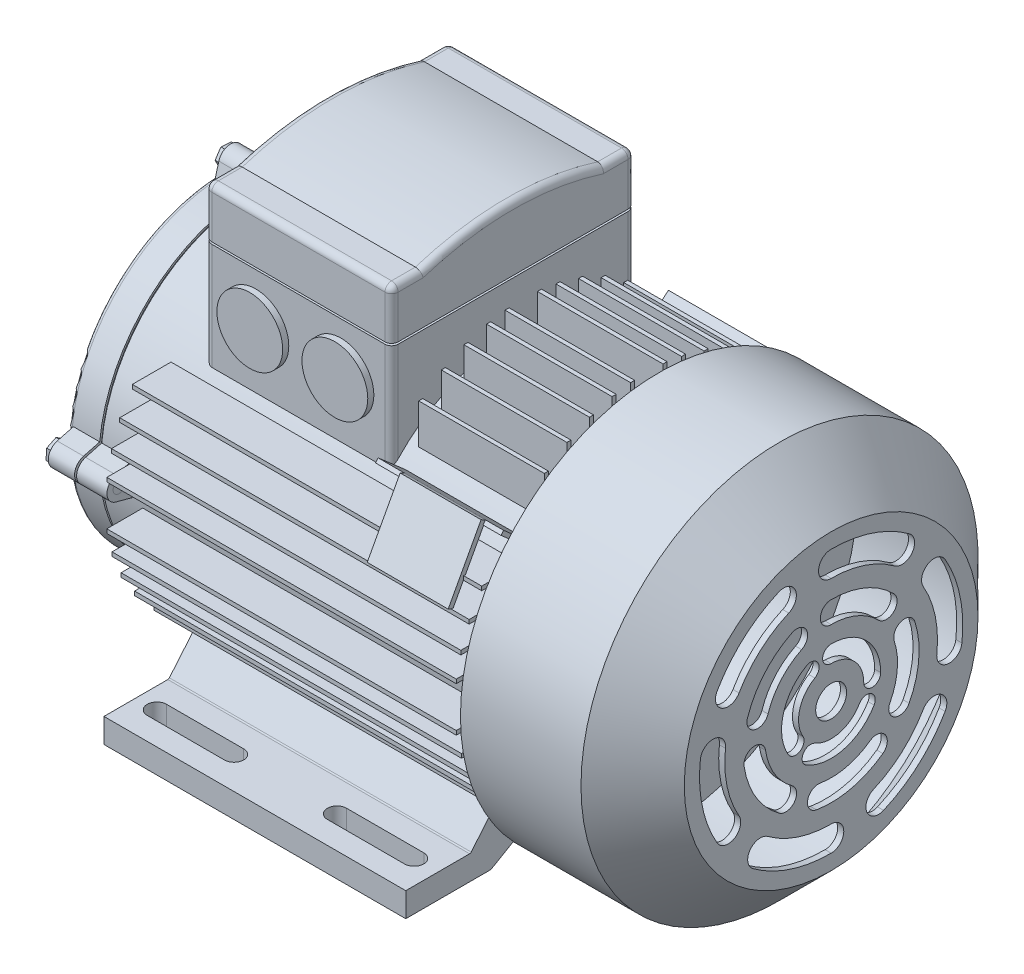
SolidWorks part; units mm, degrees
ref_plane "Front Plane" through (0, 0, 0) normal (0, 0, 1) x (1, 0, 0)
ref_plane "Top Plane" through (0, 0, 0) normal (0, 1, 0) x (1, 0, 0)
ref_plane "Right Plane" through (0, 0, 0) normal (1, 0, 0) x (0, 0, -1)
sketch "Sketch1" plane through (0, 0, 0) normal (0, 0, 1) x (1, 0, 0)
  line L0 (-1000, 0) -> (49000, 0) construction
  line L1 (0, -1000) -> (0, 49000) construction
  line L2 (0, 20) -> (0, 44.9999)
  line L3 (304.9999, 0) -> (304.9999, 72.5)
  line L4 (0, 44.9999) -> (5, 44.9999)
  line L5 (5, 44.9999) -> (5, 60)
  line L6 (5, 60) -> (6, 60)
  line L7 (6, 60) -> (6, 78)
  line L8 (6, 78) -> (219.9998, 78)
  line L9 (304.9999, 72.5) -> (279.4998, 98.0001)
  line L10 (279.4998, 98.0001) -> (219.9998, 98.0001)
  line L11 (219.9998, 98.0001) -> (219.9998, 78)
  line L12 (301.9999, 0) -> (301.9999, 71.2573)
  line L13 (301.9999, 71.2573) -> (278.2572, 95.0001)
  line L14 (278.2572, 95.0001) -> (222.9998, 95.0001)
  line L15 (222.9998, 95.0001) -> (222.9998, 68)
  line L16 (222.9998, 95.0001) -> (222.9998, 78) construction
  line L17 (222.9998, 68) -> (15, 68)
  line L18 (15, 68) -> (15, 20)
  line L19 (15, 20) -> (0, 20)
  line L20 (301.9999, 0) -> (304.9999, 0)
  dimension "D1" = 5
  dimension "D2" = 24.9999
  dimension "D3" = 39.9999
  dimension "D4" = 120
  dimension "D5" = 1
  dimension "D6" = 155.9999
  dimension "D7" = 304.9999
  dimension "D8" = 145
  dimension "D9" = 45
  dimension "D10" = 85.0001
  dimension "D11" = 196.0001
  dimension "D13" = 10
  dimension "D14" = 15
  dimension "D12" = 3
revolve "Revolve1" add sketch "Sketch1" angle 360 about L0
ref_plane "Plane1" through (43.9999, 0, 0) normal (-1, 0, 0) x (0, 0, 1)
sketch "Sketch2" plane through (43.9999, 0, 0) normal (-1, 0, 0) x (0, 0, 1)
  line L0 (-98.0001, -100.0001) -> (98.0001, -100.0001) construction
  line L1 (98.0001, -100.0001) -> (98.0001, -88.0001)
  line L2 (98.0001, -88.0001) -> (66.0001, -88.0001)
  line L3 (66.0001, -88.0001) -> (45.3874, -63.4348)
  line L4 (56.0001, -100.0001) -> (15.2779, -76.4891)
  line L5 (-98.0001, -100.0001) -> (-98.0001, -88.0001)
  line L6 (-98.0001, -88.0001) -> (-66.0001, -88.0001)
  line L7 (-66.0001, -88.0001) -> (-45.3874, -63.4348)
  line L8 (-56.0001, -100.0001) -> (-15.2779, -76.4891)
  line L9 (98.0001, -100.0001) -> (56.0001, -100.0001)
  line L10 (-56.0001, -100.0001) -> (-98.0001, -100.0001)
  circle A0 centre (0, 0) radius 68
  circle A1 centre (0, 0) radius 78
  circle A2 centre (0, 0) radius 78 construction
  circle A3 centre (0, 0) radius 68 construction
  arc A4 (-45.3874, -63.4348) -> (-15.2779, -76.4891) centre (0, 0) ccw
  arc A5 (15.2779, -76.4891) -> (45.3874, -63.4348) centre (0, 0) ccw
  point P8 (0, -100.0001)
  dimension "D1" = 100.0001
  dimension "D2" = 196.0001
  dimension "D3" = 12
  dimension "D4" = 41.9999
  dimension "D5" = 20
  dimension "D6" = 10
  dimension "D7" = 30
  dimension "D8" = 41.9999
  dimension "D9" = 20
  dimension "D10" = 10
extrude "Boss-Extrude1" add sketch "Sketch2" against normal blind 149 contours A4 L7 L6 L5 L10 L8 | L1 L2 L3 A5 L4 L9 region at (43.9999, -85.9903, -56.5508)
ref_plane "Plane2" through (102.0001, 0, 0) normal (-1, 0, 0) x (0, 0, 1)
sketch "Sketch3" plane through (102.0001, 0, 0) normal (-1, 0, 0) x (0, 0, 1)
  line L0 (98.0001, -88.0001) -> (98.0001, -100.0001)
  line L1 (66.0001, -88.0001) -> (98.0001, -88.0001)
  line L2 (45.3874, -63.4348) -> (66.0001, -88.0001)
  line L3 (15.2779, -76.4891) -> (56.0001, -100.0001)
  line L4 (56.0001, -100.0001) -> (98.0001, -100.0001)
  line L5 (-45.3874, -63.4348) -> (-66.0001, -88.0001)
  line L6 (-66.0001, -88.0001) -> (-98.0001, -88.0001)
  line L7 (-98.0001, -88.0001) -> (-98.0001, -100.0001)
  line L8 (-98.0001, -100.0001) -> (-56.0001, -100.0001)
  line L9 (-15.2779, -76.4891) -> (-56.0001, -100.0001)
  line L10 (-15.2779, -76.4891) -> (-56.0001, -100.0001) construction
  line L11 (-98.0001, -100.0001) -> (-56.0001, -100.0001) construction
  line L12 (-98.0001, -88.0001) -> (-98.0001, -100.0001) construction
  line L13 (-66.0001, -88.0001) -> (-98.0001, -88.0001) construction
  line L14 (-45.3874, -63.4348) -> (-66.0001, -88.0001) construction
  line L15 (56.0001, -100.0001) -> (98.0001, -100.0001) construction
  line L16 (15.2779, -76.4891) -> (56.0001, -100.0001) construction
  line L17 (45.3874, -63.4348) -> (66.0001, -88.0001) construction
  line L18 (66.0001, -88.0001) -> (98.0001, -88.0001) construction
  line L19 (98.0001, -88.0001) -> (98.0001, -100.0001) construction
  line L20 (0, -1000) -> (0, 49000) construction
  line L21 (-60, 128) -> (60, 128) construction
  line L22 (-60, 128) -> (-60, 49.8397)
  line L23 (60, 128) -> (60, 49.8397)
  line L24 (45, 128) -> (60, 128)
  line L25 (-45, 128) -> (-60, 128)
  circle A0 centre (0, 0) radius 68
  arc A1 (-15.2779, -76.4891) -> (15.2779, -76.4891) centre (0, 0) ccw
  arc A2 (45.3874, -63.4348) -> (-45.3874, -63.4348) centre (0, 0) ccw
  arc A3 (45.3874, -63.4348) -> (-45.3874, -63.4348) centre (0, 0) ccw construction
  arc A4 (-15.2779, -76.4891) -> (15.2779, -76.4891) centre (0, 0) ccw construction
  circle A5 centre (0, 0) radius 68 construction
  arc A6 (-60, 49.8397) -> (60, 49.8397) centre (0, 0) cw
  arc A7 (-45, 128) -> (45, 128) centre (0, -13.1434) cw
  point P21 (0, 128)
  point P28 (0, 135)
  dimension "D1" = 120
  dimension "D2" = 128
  dimension "D3" = 7
  dimension "D4" = 15
  dimension "D5" = 15
extrude "Boss-Extrude2" add sketch "Sketch3" along normal mid plane 92.0001 contours L22 A6 L23 L24 A7 L25
sketch "Sketch4" plane through (0, 0, 60) normal (0, 0, 1) x (1, 0, 0)
  line L0 (81.0001, 78.0001) -> (123, 78.0001) construction
  line L1 (102.0001, 49.8397) -> (102.0001, 128) construction
  line L4 (148.0001, 49.8397) -> (148.0001, 128)
  line L5 (148.0001, 128) -> (56, 128)
  line L6 (56, 128) -> (56, 49.8397)
  line L7 (56, 49.8397) -> (148.0001, 49.8397)
  line L8 (148.0001, 49.8397) -> (148.0001, 128)
  line L9 (148.0001, 128) -> (56, 128)
  line L10 (56, 128) -> (56, 49.8397)
  line L11 (56, 49.8397) -> (148.0001, 49.8397)
  circle A0 centre (81.0001, 78.0001) radius 16.25
  circle A1 centre (123, 78.0001) radius 16.25
  point P10 (102.0001, 78.0001)
  dimension "D3" = 32.5001
  dimension "D4" = 78.0001
  dimension "D2" = 41.9999
  dimension "D1" = 0
extrude "Boss-Extrude3" add sketch "Sketch4" along normal blind 3 contours A0 | A1 region at (81.0001, 78.0001, 60) region at (123, 78.0001, 60)
sketch "Sketch5" plane through (0, 0, 60) normal (0, 0, 1) x (1, 0, 0)
  line L0 (56, 128) -> (56, 49.8397) construction
  line L1 (56, 128) -> (148.0001, 128) construction
  point P0 (56, 103)
  dimension "D1" = 24.9999
ref_plane "Plane3" through (0, 103, 0) normal (0, 1, 0) x (1, 0, 0)
sketch "Sketch6" plane through (0, 103, 0) normal (0, 1, 0) x (1, 0, 0)
  line L0 (148.0001, 60) -> (148.0001, -60)
  line L1 (56, 60) -> (56, -60)
  line L2 (148.0001, -60) -> (56, -60)
  line L3 (148.0001, 60) -> (56, 60)
  line L4 (148.0001, 60) -> (56, 60)
  line L5 (148.0001, -60) -> (56, -60)
  line L6 (56, 60) -> (56, -60)
  line L7 (148.0001, 60) -> (148.0001, -60)
  line L8 (57, 59) -> (57, -59)
  line L9 (147.0001, -59) -> (57, -59)
  line L10 (147.0001, 59) -> (147.0001, -59)
  line L11 (147.0001, 59) -> (57, 59)
  dimension "D1" = 1
extrude "Cut-Extrude1" cut sketch "Sketch6" against normal mid plane 1 contours L11 L8 L9 L10 | L4 L6 L5 L7
ref_plane "Plane4" through (22, 0, 0) normal (-1, 0, 0) x (0, 0, 1)
sketch "Sketch7" plane through (22, 0, 0) normal (-1, 0, 0) x (0, 0, 1)
  circle A0 centre (0, 0) radius 68
  circle A1 centre (0, 0) radius 78
  circle A2 centre (0, 0) radius 78
  circle A3 centre (0, 0) radius 68 construction
  circle A4 centre (0, 0) radius 77
  dimension "D1" = 1
extrude "Cut-Extrude2" cut sketch "Sketch7" against normal mid plane 1 contours A4 | A2
sketch "Sketch8" plane through (22.5, 0, 0) normal (-1, 0, 0) x (0, 0, 1)
  line L0 (0, -1000) -> (0, 49000) construction
  line L1 (-5.7955, 85.5529) -> (-7.9276, 77.5961)
  line L2 (5.7955, 85.5529) -> (7.9276, 77.5961)
  circle A0 centre (0, 0) radius 78
  circle A1 centre (0, 0) radius 77
  circle A2 centre (0, 0) radius 68
  circle A3 centre (0, 0) radius 68 construction
  circle A4 centre (0, 0) radius 77 construction
  circle A5 centre (0, 0) radius 78 construction
  arc A6 (-5.7955, 85.5529) -> (5.7955, 85.5529) centre (0, 84) cw
  arc A7 (-7.9276, 77.5961) -> (7.9276, 77.5961) centre (0, 0) cw
  point P16 (0, 78)
  dimension "D2" = 6
  dimension "D1" = 30
  dimension "D3" = 6
extrude "Boss-Extrude4" add sketch "Sketch8" against normal blind 15
sketch "Sketch9" plane through (21.5, 0, 0) normal (1, 0, 0) x (0, 0, -1)
  line L2 (-5.7955, 85.5529) -> (-7.9276, 77.5961)
  line L3 (7.9276, 77.5961) -> (5.7955, 85.5529)
  line L4 (-5.7955, 85.5529) -> (-7.9276, 77.5961)
  line L5 (7.9276, 77.5961) -> (5.7955, 85.5529)
  circle A0 centre (0, 0) radius 77
  circle A1 centre (0, 0) radius 68
  circle A2 centre (0, 0) radius 78
  circle A3 centre (0, 0) radius 78
  circle A4 centre (0, 0) radius 68
  circle A5 centre (0, 0) radius 77
  arc A8 (-7.9276, 77.5961) -> (7.9276, 77.5961) centre (0, 0) ccw
  arc A9 (5.7955, 85.5529) -> (-5.7955, 85.5529) centre (0, 84) ccw
  arc A10 (-7.9276, 77.5961) -> (7.9276, 77.5961) centre (0, 0) ccw
  arc A11 (5.7955, 85.5529) -> (-5.7955, 85.5529) centre (0, 84) ccw
  circle M6 centre (0, 0) radius 78
  dimension "D1" = 0
extrude "Boss-Extrude5" add sketch "Sketch9" against normal blind 13 contours L5 A11 L4 M6 region at (21.5, 83.0848, 0)
sketch "Sketch10" plane through (8.5, 0, 0) normal (-1, 0, 0) x (0, 0, 1)
  circle A0 centre (0, 84) radius 3
  dimension "D1" = 6
extrude "Cut-Extrude3" cut sketch "Sketch10" against normal up to surface (28.9999 mm away) up to face at (37.4999, 82.7872, 0)
pattern_circular "CirPattern1" count 4 over 360 about axis through (-1000, 0, 0) along (-1, 0, 0) of "Cut-Extrude3", "Boss-Extrude5", "Boss-Extrude4"
fillet "Fillet1" radius 2 1 edges at (6, 0, 78)
ref_plane "Plane5" through (214.9998, 0, 0) normal (-1, 0, 0) x (0, 0, 1)
sketch "Sketch11" plane through (214.9998, 0, 0) normal (-1, 0, 0) x (0, 0, 1)
  line L0 (-1000, 0) -> (49000, 0) construction
  line L1 (95.0713, -10) -> (77.3563, -10)
  line L2 (95.0713, -10) -> (95.0713, -12)
  line L3 (95.0713, -12) -> (77.0714, -12)
  line L4 (95.0713, 10) -> (77.3563, 10)
  line L5 (95.0713, 10) -> (95.0713, 12)
  line L6 (95.0713, 12) -> (77.0714, 12)
  line L7 (92.4853, -21.1501) -> (75.0778, -21.1501)
  line L8 (92.4853, -21.1501) -> (92.4853, -23.1501)
  line L9 (92.4853, -23.1501) -> (74.4854, -23.1501)
  line L10 (88.0535, -32.3002) -> (70.9979, -32.3002)
  line L11 (88.0535, -32.3002) -> (88.0535, -34.3002)
  line L12 (88.0535, -34.3002) -> (70.0535, -34.3002)
  line L13 (81.3898, -43.4503) -> (64.7771, -43.4503)
  line L14 (81.3898, -43.4503) -> (81.3898, -45.4503)
  line L15 (81.3898, -45.4503) -> (63.3898, -45.4503)
  line L16 (71.6693, -56.6003) -> (53.6693, -56.6003)
  line L17 (71.6693, -56.6003) -> (71.6693, -54.6003)
  line L18 (71.6693, -54.6003) -> (55.7028, -54.6003)
  line L19 (88.7128, 32.3002) -> (70.9979, 32.3002)
  line L20 (88.7128, 32.3002) -> (88.7128, 34.3002)
  line L21 (88.7128, 34.3002) -> (70.0535, 34.3002)
  line L22 (92.7927, 23.1501) -> (74.4854, 23.1501)
  line L23 (92.7927, 23.1501) -> (92.7927, 21.1501)
  line L24 (92.7927, 21.1501) -> (75.0778, 21.1501)
  line L25 (82.4921, 43.4503) -> (64.7771, 43.4503)
  line L26 (82.4921, 43.4503) -> (82.4921, 45.4503)
  line L27 (82.4921, 45.4503) -> (63.3898, 45.4503)
  circle A0 centre (0, 0) radius 78
  circle A1 centre (0, 0) radius 68
  circle A2 centre (0, 0) radius 68 construction
  circle A3 centre (0, 0) radius 78
  arc A4 (55.7028, -54.6003) -> (53.6693, -56.6003) centre (0, 0) cw
  dimension "D1" = 10
  dimension "D2" = 10
  dimension "D3" = 2
  dimension "D4" = 17.715
  dimension "D5" = 18
  dimension "D6" = 11.1501
  dimension "D7" = 11.1501
  dimension "D8" = 11.1501
  dimension "D9" = 11.1501
  dimension "D10" = 11.1501
  dimension "D11" = 11.1501
  dimension "D12" = 11.1501
ref_plane "Plane6" through (42.4999, 0, 0) normal (1, 0, 0) x (0, 0, -1)
extrude "Boss-Extrude6" add sketch "Sketch11" along normal up to surface (172.4999 mm away) contours A3 L25 L26 L27 | A3 L19 L20 L21 | A3 L24 L23 L22 | A3 L4 L5 L6 | A3 L3 L2 L1 | A3 L9 L8 L7 | A3 L12 L11 L10 | A3 L15 L14 L13 | A3 L16 L17 L18 region at (214.9998, -11.0026, 86.1446) region at (214.9998, -22.1556, 83.635) region at (214.9998, 11.0026, 86.1446) region at (214.9998, -33.3091, 79.2903) region at (214.9998, 22.1556, 83.7888) region at (214.9998, -44.4636, 72.7358) region at (214.9998, 33.3088, 79.6201) region at (214.9998, -55.6203, 63.1737) region at (214.9998, 44.4628, 73.2873) up to plane "Plane6"
sketch "Sketch12" plane through (214.9998, 0, 0) normal (1, 0, 0) x (0, 0, -1)
  line L0 (-71.6693, -56.6003) -> (-53.6693, -56.6003)
  line L1 (-71.6693, -56.6003) -> (-71.6693, -54.6003)
  line L2 (-71.6693, -54.6003) -> (-55.7028, -54.6003)
  line L3 (-81.3898, -45.4503) -> (-63.3898, -45.4503)
  line L4 (-81.3898, -43.4503) -> (-81.3898, -45.4503)
  line L5 (-81.3898, -43.4503) -> (-64.7771, -43.4503)
  line L6 (-88.0535, -34.3002) -> (-70.0535, -34.3002)
  line L7 (-88.0535, -32.3002) -> (-88.0535, -34.3002)
  line L8 (-88.0535, -32.3002) -> (-70.9979, -32.3002)
  line L9 (-92.4853, -23.1501) -> (-74.4854, -23.1501)
  line L10 (-92.4853, -21.1501) -> (-92.4853, -23.1501)
  line L11 (-92.4853, -21.1501) -> (-75.0778, -21.1501)
  line L12 (-95.0713, -12) -> (-77.0714, -12)
  line L13 (-95.0713, -10) -> (-95.0713, -12)
  line L14 (-95.0713, -10) -> (-77.3563, -10)
  line L15 (-95.0713, 10) -> (-77.3563, 10)
  line L16 (-95.0713, 10) -> (-95.0713, 12)
  line L17 (-95.0713, 12) -> (-77.0714, 12)
  line L18 (-92.7927, 21.1501) -> (-75.0778, 21.1501)
  line L19 (-92.7927, 23.1501) -> (-92.7927, 21.1501)
  line L20 (-92.7927, 23.1501) -> (-74.4854, 23.1501)
  line L21 (-88.7128, 32.3002) -> (-70.9979, 32.3002)
  line L22 (-88.7128, 32.3002) -> (-88.7128, 34.3002)
  line L23 (-88.7128, 34.3002) -> (-70.0535, 34.3002)
  line L24 (-82.4921, 43.4503) -> (-64.7771, 43.4503)
  line L25 (-82.4921, 43.4503) -> (-82.4921, 45.4503)
  line L26 (-82.4921, 45.4503) -> (-63.3898, 45.4503)
  line L27 (-82.4921, 45.4503) -> (-63.3898, 45.4503)
  line L28 (-82.4921, 43.4503) -> (-82.4921, 45.4503)
  line L29 (-82.4921, 43.4503) -> (-64.7771, 43.4503)
  line L30 (-88.7128, 34.3002) -> (-70.0535, 34.3002)
  line L31 (-88.7128, 32.3002) -> (-88.7128, 34.3002)
  line L32 (-88.7128, 32.3002) -> (-70.9979, 32.3002)
  line L33 (-92.7927, 23.1501) -> (-74.4854, 23.1501)
  line L34 (-92.7927, 23.1501) -> (-92.7927, 21.1501)
  line L35 (-92.7927, 21.1501) -> (-75.0778, 21.1501)
  line L36 (-95.0713, 12) -> (-77.0714, 12)
  line L37 (-95.0713, 10) -> (-95.0713, 12)
  line L38 (-95.0713, 10) -> (-77.3563, 10)
  line L39 (-95.0713, -10) -> (-77.3563, -10)
  line L40 (-95.0713, -10) -> (-95.0713, -12)
  line L41 (-95.0713, -12) -> (-77.0714, -12)
  line L42 (-92.4853, -21.1501) -> (-75.0778, -21.1501)
  line L43 (-92.4853, -21.1501) -> (-92.4853, -23.1501)
  line L44 (-92.4853, -23.1501) -> (-74.4854, -23.1501)
  line L45 (-88.0535, -32.3002) -> (-70.9979, -32.3002)
  line L46 (-88.0535, -32.3002) -> (-88.0535, -34.3002)
  line L47 (-88.0535, -34.3002) -> (-70.0535, -34.3002)
  line L48 (-81.3898, -43.4503) -> (-64.7771, -43.4503)
  line L49 (-81.3898, -43.4503) -> (-81.3898, -45.4503)
  line L50 (-81.3898, -45.4503) -> (-63.3898, -45.4503)
  line L51 (-71.6693, -54.6003) -> (-55.7028, -54.6003)
  line L52 (-71.6693, -56.6003) -> (-71.6693, -54.6003)
  line L53 (-71.6693, -56.6003) -> (-53.6693, -56.6003)
  line L54 (0, -1000) -> (0, 49000) construction
  line L55 (-7, 95.6852) -> (-7, 77.6852)
  line L56 (-7, 95.6852) -> (-9, 95.6852)
  line L57 (-9, 95.6852) -> (-9, 77.479)
  line L58 (-18.1501, 94.3097) -> (-18.1501, 75.8589)
  line L59 (-18.1501, 94.3097) -> (-16.1501, 94.3097)
  line L60 (-16.1501, 94.3097) -> (-16.1501, 76.3097)
  line L61 (-27.3002, 91.0663) -> (-27.3002, 73.0664)
  line L62 (-27.3002, 91.0663) -> (-29.3002, 91.0663)
  line L63 (-29.3002, 91.0663) -> (-29.3002, 72.2876)
  line L64 (-38.4503, 85.8643) -> (-38.4503, 67.8644)
  line L65 (-38.4503, 85.8643) -> (-40.4503, 85.8643)
  line L66 (-40.4503, 85.8643) -> (-40.4503, 66.6916)
  line L67 (-49.6004, 78.198) -> (-49.6004, 60.198)
  line L68 (-49.6004, 78.198) -> (-51.6004, 78.198)
  line L69 (-51.6004, 78.198) -> (-51.6004, 58.4927)
  circle A0 centre (0, 0) radius 68
  arc A1 (-63.3898, 45.4503) -> (-64.7771, 43.4503) centre (0, 0) ccw
  arc A2 (-64.7771, 43.4503) -> (-70.0535, 34.3002) centre (0, 0) ccw
  arc A3 (-70.0535, 34.3002) -> (-70.9979, 32.3002) centre (0, 0) ccw
  arc A4 (-70.9979, 32.3002) -> (-74.4854, 23.1501) centre (0, 0) ccw
  arc A5 (-74.4854, 23.1501) -> (-75.0778, 21.1501) centre (0, 0) ccw
  arc A6 (-75.0778, 21.1501) -> (-77.0714, 12) centre (0, 0) ccw
  arc A7 (-77.0714, 12) -> (-77.3563, 10) centre (0, 0) ccw
  arc A8 (-77.3563, 10) -> (-77.3563, -10) centre (0, 0) ccw
  arc A9 (-77.3563, -10) -> (-77.0714, -12) centre (0, 0) ccw
  arc A10 (-77.0714, -12) -> (-75.0778, -21.1501) centre (0, 0) ccw
  arc A11 (-75.0778, -21.1501) -> (-74.4854, -23.1501) centre (0, 0) ccw
  arc A12 (-74.4854, -23.1501) -> (-70.9979, -32.3002) centre (0, 0) ccw
  arc A13 (-70.9979, -32.3002) -> (-70.0535, -34.3002) centre (0, 0) ccw
  arc A14 (-70.0535, -34.3002) -> (-64.7771, -43.4503) centre (0, 0) ccw
  arc A15 (-64.7771, -43.4503) -> (-63.3898, -45.4503) centre (0, 0) ccw
  arc A16 (-63.3898, -45.4503) -> (-55.7028, -54.6003) centre (0, 0) ccw
  arc A17 (-55.7028, -54.6003) -> (-53.6693, -56.6003) centre (0, 0) ccw
  arc A18 (-53.6693, -56.6003) -> (-63.3898, 45.4503) centre (0, 0) ccw
  arc A19 (-53.6693, -56.6003) -> (-63.3898, 45.4503) centre (0, 0) ccw
  arc A20 (-55.7028, -54.6003) -> (-53.6693, -56.6003) centre (0, 0) ccw
  arc A21 (-63.3898, -45.4503) -> (-55.7028, -54.6003) centre (0, 0) ccw
  arc A22 (-64.7771, -43.4503) -> (-63.3898, -45.4503) centre (0, 0) ccw
  arc A23 (-70.0535, -34.3002) -> (-64.7771, -43.4503) centre (0, 0) ccw
  arc A24 (-70.9979, -32.3002) -> (-70.0535, -34.3002) centre (0, 0) ccw
  arc A25 (-74.4854, -23.1501) -> (-70.9979, -32.3002) centre (0, 0) ccw
  arc A26 (-75.0778, -21.1501) -> (-74.4854, -23.1501) centre (0, 0) ccw
  arc A27 (-77.0714, -12) -> (-75.0778, -21.1501) centre (0, 0) ccw
  arc A28 (-77.3563, -10) -> (-77.0714, -12) centre (0, 0) ccw
  arc A29 (-77.3563, 10) -> (-77.3563, -10) centre (0, 0) ccw
  arc A30 (-77.0714, 12) -> (-77.3563, 10) centre (0, 0) ccw
  arc A31 (-75.0778, 21.1501) -> (-77.0714, 12) centre (0, 0) ccw
  arc A32 (-74.4854, 23.1501) -> (-75.0778, 21.1501) centre (0, 0) ccw
  arc A33 (-70.9979, 32.3002) -> (-74.4854, 23.1501) centre (0, 0) ccw
  arc A34 (-70.0535, 34.3002) -> (-70.9979, 32.3002) centre (0, 0) ccw
  arc A35 (-64.7771, 43.4503) -> (-70.0535, 34.3002) centre (0, 0) ccw
  arc A36 (-63.3898, 45.4503) -> (-64.7771, 43.4503) centre (0, 0) ccw
  circle A37 centre (0, 0) radius 68 construction
  dimension "D3" = 2
  dimension "D6" = 11.1501
  dimension "D7" = 11.1501
  dimension "D1" = 18
  dimension "D2" = 7
  dimension "D4" = 11.1501
  dimension "D5" = 11.1501
ref_plane "Plane7" through (153.0001, 0, 0) normal (1, 0, 0) x (0, 0, -1)
extrude "Boss-Extrude7" add sketch "Sketch12" against normal up to surface (61.9997 mm away) contours A19 L67 L68 L69 | A19 L64 L65 L66 | A19 L61 L62 L63 | A19 L60 L59 L58 | A19 L55 L56 L57 region at (214.9998, 86.6357, 8.0019) region at (214.9998, 85.1988, 17.1542) region at (214.9998, 81.8729, 28.3072) region at (214.9998, 76.5714, 39.4608) region at (214.9998, 68.7701, 50.6154) up to plane "Plane7"
sketch "Sketch13" plane through (214.9998, 0, 0) normal (1, 0, 0) x (0, 0, -1)
  line L0 (-9, 95.6852) -> (-9, 77.479)
  line L1 (-7, 95.6852) -> (-9, 95.6852)
  line L2 (-7, 95.6852) -> (-7, 77.6852)
  line L3 (-18.1501, 94.3097) -> (-18.1501, 75.8589)
  line L4 (-18.1501, 94.3097) -> (-16.1501, 94.3097)
  line L5 (-16.1501, 94.3097) -> (-16.1501, 76.3097)
  line L6 (-29.3002, 91.0663) -> (-29.3002, 72.2876)
  line L7 (-27.3002, 91.0663) -> (-29.3002, 91.0663)
  line L8 (-27.3002, 91.0663) -> (-27.3002, 73.0664)
  line L9 (-40.4503, 85.8643) -> (-40.4503, 66.6916)
  line L10 (-38.4503, 85.8643) -> (-40.4503, 85.8643)
  line L11 (-38.4503, 85.8643) -> (-38.4503, 67.8644)
  line L12 (-51.6004, 78.198) -> (-51.6004, 58.4927)
  line L13 (-49.6004, 78.198) -> (-51.6004, 78.198)
  line L14 (-49.6004, 78.198) -> (-49.6004, 60.198)
  line L15 (-71.6693, -56.6003) -> (-53.6693, -56.6003)
  line L16 (-71.6693, -56.6003) -> (-71.6693, -54.6003)
  line L17 (-71.6693, -54.6003) -> (-55.7028, -54.6003)
  line L18 (-81.3898, -45.4503) -> (-63.3898, -45.4503)
  line L19 (-81.3898, -43.4503) -> (-81.3898, -45.4503)
  line L20 (-81.3898, -43.4503) -> (-64.7771, -43.4503)
  line L21 (-88.0535, -34.3002) -> (-70.0535, -34.3002)
  line L22 (-88.0535, -32.3002) -> (-88.0535, -34.3002)
  line L23 (-88.0535, -32.3002) -> (-70.9979, -32.3002)
  line L24 (-92.4853, -23.1501) -> (-74.4854, -23.1501)
  line L25 (-92.4853, -21.1501) -> (-92.4853, -23.1501)
  line L26 (-92.4853, -21.1501) -> (-75.0778, -21.1501)
  line L27 (-95.0713, -12) -> (-77.0714, -12)
  line L28 (-95.0713, -10) -> (-95.0713, -12)
  line L29 (-95.0713, -10) -> (-77.3563, -10)
  line L30 (-95.0713, 10) -> (-77.3563, 10)
  line L31 (-95.0713, 10) -> (-95.0713, 12)
  line L32 (-95.0713, 12) -> (-77.0714, 12)
  line L33 (-92.7927, 21.1501) -> (-75.0778, 21.1501)
  line L34 (-92.7927, 23.1501) -> (-92.7927, 21.1501)
  line L35 (-92.7927, 23.1501) -> (-74.4854, 23.1501)
  line L36 (-88.7128, 32.3002) -> (-70.9979, 32.3002)
  line L37 (-88.7128, 32.3002) -> (-88.7128, 34.3002)
  line L38 (-88.7128, 34.3002) -> (-70.0535, 34.3002)
  line L39 (-82.4921, 43.4503) -> (-64.7771, 43.4503)
  line L40 (-82.4921, 43.4503) -> (-82.4921, 45.4503)
  line L41 (-82.4921, 45.4503) -> (-63.3898, 45.4503)
  line L42 (-82.4921, 45.4503) -> (-63.3898, 45.4503)
  line L43 (-82.4921, 43.4503) -> (-82.4921, 45.4503)
  line L44 (-82.4921, 43.4503) -> (-64.7771, 43.4503)
  line L45 (-88.7128, 34.3002) -> (-70.0535, 34.3002)
  line L46 (-88.7128, 32.3002) -> (-88.7128, 34.3002)
  line L47 (-88.7128, 32.3002) -> (-70.9979, 32.3002)
  line L48 (-92.7927, 23.1501) -> (-74.4854, 23.1501)
  line L49 (-92.7927, 23.1501) -> (-92.7927, 21.1501)
  line L50 (-92.7927, 21.1501) -> (-75.0778, 21.1501)
  line L51 (-95.0713, 12) -> (-77.0714, 12)
  line L52 (-95.0713, 10) -> (-95.0713, 12)
  line L53 (-95.0713, 10) -> (-77.3563, 10)
  line L54 (-95.0713, -10) -> (-77.3563, -10)
  line L55 (-95.0713, -10) -> (-95.0713, -12)
  line L56 (-95.0713, -12) -> (-77.0714, -12)
  line L57 (-92.4853, -21.1501) -> (-75.0778, -21.1501)
  line L58 (-92.4853, -21.1501) -> (-92.4853, -23.1501)
  line L59 (-92.4853, -23.1501) -> (-74.4854, -23.1501)
  line L60 (-88.0535, -32.3002) -> (-70.9979, -32.3002)
  line L61 (-88.0535, -32.3002) -> (-88.0535, -34.3002)
  line L62 (-88.0535, -34.3002) -> (-70.0535, -34.3002)
  line L63 (-81.3898, -43.4503) -> (-64.7771, -43.4503)
  line L64 (-81.3898, -43.4503) -> (-81.3898, -45.4503)
  line L65 (-81.3898, -45.4503) -> (-63.3898, -45.4503)
  line L66 (-71.6693, -54.6003) -> (-55.7028, -54.6003)
  line L67 (-71.6693, -56.6003) -> (-71.6693, -54.6003)
  line L68 (-71.6693, -56.6003) -> (-53.6693, -56.6003)
  line L69 (-49.6004, 78.198) -> (-49.6004, 60.198)
  line L70 (-49.6004, 78.198) -> (-51.6004, 78.198)
  line L71 (-51.6004, 78.198) -> (-51.6004, 58.4927)
  line L72 (-38.4503, 85.8643) -> (-38.4503, 67.8644)
  line L73 (-38.4503, 85.8643) -> (-40.4503, 85.8643)
  line L74 (-40.4503, 85.8643) -> (-40.4503, 66.6916)
  line L75 (-27.3002, 91.0663) -> (-27.3002, 73.0664)
  line L76 (-27.3002, 91.0663) -> (-29.3002, 91.0663)
  line L77 (-29.3002, 91.0663) -> (-29.3002, 72.2876)
  line L78 (-16.1501, 94.3097) -> (-16.1501, 76.3097)
  line L79 (-18.1501, 94.3097) -> (-16.1501, 94.3097)
  line L80 (-18.1501, 94.3097) -> (-18.1501, 75.8589)
  line L81 (-7, 95.6852) -> (-7, 77.6852)
  line L82 (-7, 95.6852) -> (-9, 95.6852)
  line L83 (-9, 95.6852) -> (-9, 77.479)
  line L84 (-71.6612, 63.8782) -> (-58.1005, 52.0416)
  line L85 (-72.9764, 62.3714) -> (-59.4157, 50.5348)
  line L86 (-71.6612, 63.8782) -> (-72.9764, 62.3714)
  circle A0 centre (0, 0) radius 68
  arc A1 (-7, 77.6852) -> (-9, 77.479) centre (0, 0) ccw
  arc A2 (-9, 77.479) -> (-16.1501, 76.3097) centre (0, 0) ccw
  arc A3 (-16.1501, 76.3097) -> (-18.1501, 75.8589) centre (0, 0) ccw
  arc A4 (-18.1501, 75.8589) -> (-27.3002, 73.0664) centre (0, 0) ccw
  arc A5 (-27.3002, 73.0664) -> (-29.3002, 72.2876) centre (0, 0) ccw
  arc A6 (-29.3002, 72.2876) -> (-38.4503, 67.8644) centre (0, 0) ccw
  arc A7 (-38.4503, 67.8644) -> (-40.4503, 66.6916) centre (0, 0) ccw
  arc A8 (-40.4503, 66.6916) -> (-49.6004, 60.198) centre (0, 0) ccw
  arc A9 (-49.6004, 60.198) -> (-51.6004, 58.4927) centre (0, 0) ccw
  arc A10 (-51.6004, 58.4927) -> (-63.3898, 45.4503) centre (0, 0) ccw
  arc A11 (-63.3898, 45.4503) -> (-64.7771, 43.4503) centre (0, 0) ccw
  arc A12 (-64.7771, 43.4503) -> (-70.0535, 34.3002) centre (0, 0) ccw
  arc A13 (-70.0535, 34.3002) -> (-70.9979, 32.3002) centre (0, 0) ccw
  arc A14 (-70.9979, 32.3002) -> (-74.4854, 23.1501) centre (0, 0) ccw
  arc A15 (-74.4854, 23.1501) -> (-75.0778, 21.1501) centre (0, 0) ccw
  arc A16 (-75.0778, 21.1501) -> (-77.0714, 12) centre (0, 0) ccw
  arc A17 (-77.0714, 12) -> (-77.3563, 10) centre (0, 0) ccw
  arc A18 (-77.3563, 10) -> (-77.3563, -10) centre (0, 0) ccw
  arc A19 (-77.3563, -10) -> (-77.0714, -12) centre (0, 0) ccw
  arc A20 (-77.0714, -12) -> (-75.0778, -21.1501) centre (0, 0) ccw
  arc A21 (-75.0778, -21.1501) -> (-74.4854, -23.1501) centre (0, 0) ccw
  arc A22 (-74.4854, -23.1501) -> (-70.9979, -32.3002) centre (0, 0) ccw
  arc A23 (-70.9979, -32.3002) -> (-70.0535, -34.3002) centre (0, 0) ccw
  arc A24 (-70.0535, -34.3002) -> (-64.7771, -43.4503) centre (0, 0) ccw
  arc A25 (-64.7771, -43.4503) -> (-63.3898, -45.4503) centre (0, 0) ccw
  arc A26 (-63.3898, -45.4503) -> (-55.7028, -54.6003) centre (0, 0) ccw
  arc A27 (-55.7028, -54.6003) -> (-53.6693, -56.6003) centre (0, 0) ccw
  arc A28 (-53.6693, -56.6003) -> (-7, 77.6852) centre (0, 0) ccw
  arc A29 (-53.6693, -56.6003) -> (-7, 77.6852) centre (0, 0) ccw
  arc A30 (-55.7028, -54.6003) -> (-53.6693, -56.6003) centre (0, 0) ccw
  arc A31 (-63.3898, -45.4503) -> (-55.7028, -54.6003) centre (0, 0) ccw
  arc A32 (-64.7771, -43.4503) -> (-63.3898, -45.4503) centre (0, 0) ccw
  arc A33 (-70.0535, -34.3002) -> (-64.7771, -43.4503) centre (0, 0) ccw
  arc A34 (-70.9979, -32.3002) -> (-70.0535, -34.3002) centre (0, 0) ccw
  arc A35 (-74.4854, -23.1501) -> (-70.9979, -32.3002) centre (0, 0) ccw
  arc A36 (-75.0778, -21.1501) -> (-74.4854, -23.1501) centre (0, 0) ccw
  arc A37 (-77.0714, -12) -> (-75.0778, -21.1501) centre (0, 0) ccw
  arc A38 (-77.3563, -10) -> (-77.0714, -12) centre (0, 0) ccw
  arc A39 (-77.3563, 10) -> (-77.3563, -10) centre (0, 0) ccw
  arc A40 (-77.0714, 12) -> (-77.3563, 10) centre (0, 0) ccw
  arc A41 (-75.0778, 21.1501) -> (-77.0714, 12) centre (0, 0) ccw
  arc A42 (-74.4854, 23.1501) -> (-75.0778, 21.1501) centre (0, 0) ccw
  arc A43 (-70.9979, 32.3002) -> (-74.4854, 23.1501) centre (0, 0) ccw
  arc A44 (-70.0535, 34.3002) -> (-70.9979, 32.3002) centre (0, 0) ccw
  arc A45 (-64.7771, 43.4503) -> (-70.0535, 34.3002) centre (0, 0) ccw
  arc A46 (-63.3898, 45.4503) -> (-64.7771, 43.4503) centre (0, 0) ccw
  arc A47 (-51.6004, 58.4927) -> (-63.3898, 45.4503) centre (0, 0) ccw
  arc A48 (-49.6004, 60.198) -> (-51.6004, 58.4927) centre (0, 0) ccw
  arc A49 (-40.4503, 66.6916) -> (-49.6004, 60.198) centre (0, 0) ccw
  arc A50 (-38.4503, 67.8644) -> (-40.4503, 66.6916) centre (0, 0) ccw
  arc A51 (-29.3002, 72.2876) -> (-38.4503, 67.8644) centre (0, 0) ccw
  arc A52 (-27.3002, 73.0664) -> (-29.3002, 72.2876) centre (0, 0) ccw
  arc A53 (-18.1501, 75.8589) -> (-27.3002, 73.0664) centre (0, 0) ccw
  arc A54 (-16.1501, 76.3097) -> (-18.1501, 75.8589) centre (0, 0) ccw
  arc A55 (-9, 77.479) -> (-16.1501, 76.3097) centre (0, 0) ccw
  arc A56 (-7, 77.6852) -> (-9, 77.479) centre (0, 0) ccw
  circle A57 centre (0, 0) radius 68
  dimension "D1" = 41.116
  dimension "D2" = 2
  dimension "D3" = 5.0846
  dimension "D4" = 18
extrude "Boss-Extrude8" add sketch "Sketch13" against normal up to surface (61.9997 mm away) contours A47 L84 L86 L85 region at (214.9998, 57.2079, 65.5401) up to face at (153.0001, 68.7738, 50.6022)
mirror "Mirror1" about plane through (0, 0, 0) normal (0, 0, 1) of "Boss-Extrude6", "Boss-Extrude7", "Boss-Extrude8"
fillet "Fillet2" radius 3.2499 12 edges at (148.0001, 76.1699, -60) (148.0001, 115.75, -60) (148.0001, 76.1699, 60) (148.0001, 115.75, 60) (56, 76.1699, -60) (56, 115.75, -60) (56, 76.1699, 60) (56, 115.75, 60) (147.0001, 103, 59) (147.0001, 103, -59) (57, 103, -59) (57, 103, 59)
fillet "Fillet3" radius 3.2499 12 edges at (56, 128, -50.8751) (56.9519, 128, -59.0481) (102.0001, 128, -60) (147.0482, 128, -59.0481) (148.0001, 128, 50.8751) (147.0482, 128, 59.0481) (102.0001, 128, 60) (56.9519, 128, 59.0481) (56, 135, 0) (148.0001, 128, -50.8751) (148.0001, 135, 0) (56, 128, 50.8751)
fillet "Fillet4" radius 2 2 edges at (118.4999, -100.0001, 56.0001) (118.4999, -100.0001, -56.0001)
fillet "Fillet5" radius 1 2 edges at (118.4999, -88.0001, -66.0001) (118.4999, -88.0001, 66.0001)
sketch "Sketch14" plane through (0, -88.0001, 0) normal (0, 1, 0) x (1, 0, 0)
  line L0 (43.9999, -98.0001) -> (43.9999, -66.4664) construction
  line L1 (54.2534, -77.3626) -> (92.3534, -77.3626)
  line L2 (54.2534, -77.3626) -> (54.2534, -86.8876) construction
  line L3 (54.2534, -86.8876) -> (92.3534, -86.8876)
  line L4 (92.3534, -77.3626) -> (92.3534, -86.8876) construction
  line L5 (192.9999, -98.0001) -> (43.9999, -98.0001) construction
  circle A0 centre (54.2534, -82.1251) radius 4.7625 construction
  circle A1 centre (92.3534, -82.1251) radius 4.7625 construction
  arc A2 (54.2534, -77.3626) -> (54.2534, -86.8876) centre (54.2534, -82.1251) ccw
  arc A3 (92.3534, -77.3626) -> (92.3534, -86.8876) centre (92.3534, -82.1251) cw
  dimension "D4" = 15.875
  dimension "D1" = 9.525
  dimension "D2" = 38.1
  dimension "D3" = 10.2535
extrude "Cut-Extrude4" cut sketch "Sketch14" against normal through all
pattern_linear "LPattern1" count 2 spacing 88.9 along (1, 0, 0) count 2 spacing 165.1 along (0, 0, -1) of "Cut-Extrude4"
sketch "Sketch15" plane through (304.9999, 0, 0) normal (1, 0, 0) x (0, 0, -1)
  circle A0 centre (0, 0) radius 7.62
  circle A1 centre (0, 0) radius 20.2842 construction
  arc A2 (0, 20.2842) -> (20.2842, 0) centre (0, 0) cw construction
  arc A3 (24.4729, 0) -> (0, 24.4729) centre (0, 0) ccw
  arc A4 (16.0956, 0) -> (0, 16.0956) centre (0, 0) ccw
  arc A5 (16.0956, 0) -> (24.4729, 0) centre (20.2842, 0) ccw
  arc A6 (0, 24.4729) -> (0, 16.0956) centre (0, 20.2842) ccw
  arc A7 (17.5667, -10.1421) -> (-10.1421, -17.5667) centre (0, 0) cw construction
  arc A8 (-12.2365, -21.1942) -> (21.1942, -12.2365) centre (0, 0) ccw
  arc A9 (-8.0478, -13.9392) -> (13.9392, -8.0478) centre (0, 0) ccw
  arc A10 (-8.0478, -13.9392) -> (-12.2365, -21.1942) centre (-10.1421, -17.5667) ccw
  arc A11 (21.1942, -12.2365) -> (13.9392, -8.0478) centre (17.5667, -10.1421) ccw
  arc A12 (-17.5667, -10.1421) -> (-10.1421, 17.5667) centre (0, 0) cw construction
  arc A13 (-12.2365, 21.1942) -> (-21.1942, -12.2365) centre (0, 0) ccw
  arc A14 (-8.0478, 13.9392) -> (-13.9392, -8.0478) centre (0, 0) ccw
  arc A15 (-8.0478, 13.9392) -> (-12.2365, 21.1942) centre (-10.1421, 17.5667) ccw
  arc A16 (-21.1942, -12.2365) -> (-13.9392, -8.0478) centre (-17.5667, -10.1421) ccw
  circle A17 centre (0, 0) radius 38.1 construction
  arc A18 (0, 38.1) -> (27.2217, 26.6569) centre (0, 0) cw construction
  arc A19 (31.0311, 30.3873) -> (0, 43.4318) centre (0, 0) ccw
  arc A20 (23.4122, 22.9265) -> (0, 32.7682) centre (0, 0) ccw
  arc A21 (23.4122, 22.9265) -> (31.0311, 30.3873) centre (27.2217, 26.6569) ccw
  arc A22 (0, 43.4318) -> (0, 32.7682) centre (0, 38.1) ccw
  arc A23 (36.2353, 11.7735) -> (33.7642, -17.6519) centre (0, 0) cw construction
  arc A24 (38.4892, -20.1222) -> (41.3061, 13.4212) centre (0, 0) ccw
  arc A25 (29.0391, -15.1817) -> (31.1644, 10.1259) centre (0, 0) ccw
  arc A26 (29.0391, -15.1817) -> (38.4892, -20.1222) centre (33.7642, -17.6519) ccw
  arc A27 (41.3061, 13.4212) -> (31.1644, 10.1259) centre (36.2353, 11.7735) ccw
  arc A28 (22.3946, -30.8235) -> (-6.3542, -37.5664) centre (0, 0) cw construction
  arc A29 (-7.2435, -42.8235) -> (25.5286, -35.1371) centre (0, 0) ccw
  arc A30 (-5.465, -32.3093) -> (19.2607, -26.51) centre (0, 0) ccw
  arc A31 (-5.465, -32.3093) -> (-7.2435, -42.8235) centre (-6.3542, -37.5664) ccw
  arc A32 (25.5286, -35.1371) -> (19.2607, -26.51) centre (22.3946, -30.8235) ccw
  arc A33 (-22.3946, -30.8235) -> (-37.6913, -5.5654) centre (0, 0) cw construction
  arc A34 (-42.966, -6.3442) -> (-25.5286, -35.1371) centre (0, 0) ccw
  arc A35 (-32.4167, -4.7866) -> (-19.2607, -26.51) centre (0, 0) ccw
  arc A36 (-32.4167, -4.7866) -> (-42.966, -6.3442) centre (-37.6913, -5.5654) ccw
  arc A37 (-25.5286, -35.1371) -> (-19.2607, -26.51) centre (-22.3946, -30.8235) ccw
  arc A38 (-36.2353, 11.7735) -> (-16.9403, 34.1268) centre (0, 0) cw construction
  arc A39 (-19.3109, 38.9026) -> (-41.3061, 13.4212) centre (0, 0) ccw
  arc A40 (-14.5696, 29.351) -> (-31.1644, 10.1259) centre (0, 0) ccw
  arc A41 (-14.5696, 29.351) -> (-19.3109, 38.9026) centre (-16.9403, 34.1268) ccw
  arc A42 (-41.3061, 13.4212) -> (-31.1644, 10.1259) centre (-36.2353, 11.7735) ccw
  circle A43 centre (0, 0) radius 58.7483 construction
  arc A44 (0, 58.7483) -> (34.9665, 47.2091) centre (0, 0) cw construction
  arc A45 (38.6785, 52.2208) -> (0, 64.9849) centre (0, 0) ccw
  arc A46 (31.2545, 42.1975) -> (0, 52.5116) centre (0, 0) ccw
  arc A47 (31.2545, 42.1975) -> (38.6785, 52.2208) centre (34.9665, 47.2091) ccw
  arc A48 (0, 64.9849) -> (0, 52.5116) centre (0, 58.7483) ccw
  arc A49 (50.8775, 29.3741) -> (58.3676, -6.6773) centre (0, 0) cw construction
  arc A50 (64.5638, -7.3861) -> (56.2786, 32.4924) centre (0, 0) ccw
  arc A51 (52.1713, -5.9684) -> (45.4764, 26.2558) centre (0, 0) ccw
  arc A52 (52.1713, -5.9684) -> (64.5638, -7.3861) centre (58.3676, -6.6773) ccw
  arc A53 (56.2786, 32.4924) -> (45.4764, 26.2558) centre (50.8775, 29.3741) ccw
  arc A54 (50.8775, -29.3741) -> (23.4011, -53.8864) centre (0, 0) cw construction
  arc A55 (25.8853, -59.6069) -> (56.2786, -32.4924) centre (0, 0) ccw
  arc A56 (20.9169, -48.1659) -> (45.4764, -26.2558) centre (0, 0) ccw
  arc A57 (20.9169, -48.1659) -> (25.8853, -59.6069) centre (23.4011, -53.8864) ccw
  arc A58 (56.2786, -32.4924) -> (45.4764, -26.2558) centre (50.8775, -29.3741) ccw
  arc A59 (0, -58.7483) -> (-34.9665, -47.2091) centre (0, 0) cw construction
  arc A60 (-38.6785, -52.2208) -> (0, -64.9849) centre (0, 0) ccw
  arc A61 (-31.2545, -42.1975) -> (0, -52.5116) centre (0, 0) ccw
  arc A62 (-31.2545, -42.1975) -> (-38.6785, -52.2208) centre (-34.9665, -47.2091) ccw
  arc A63 (0, -64.9849) -> (0, -52.5116) centre (0, -58.7483) ccw
  arc A64 (-50.8775, -29.3741) -> (-58.3676, 6.6773) centre (0, 0) cw construction
  arc A65 (-64.5638, 7.3861) -> (-56.2786, -32.4924) centre (0, 0) ccw
  arc A66 (-52.1713, 5.9684) -> (-45.4764, -26.2558) centre (0, 0) ccw
  arc A67 (-52.1713, 5.9684) -> (-64.5638, 7.3861) centre (-58.3676, 6.6773) ccw
  arc A68 (-56.2786, -32.4924) -> (-45.4764, -26.2558) centre (-50.8775, -29.3741) ccw
  arc A69 (-50.8775, 29.3741) -> (-23.4011, 53.8864) centre (0, 0) cw construction
  arc A70 (-25.8853, 59.6069) -> (-56.2786, 32.4924) centre (0, 0) ccw
  arc A71 (-20.9169, 48.1659) -> (-45.4764, 26.2558) centre (0, 0) ccw
  arc A72 (-20.9169, 48.1659) -> (-25.8853, 59.6069) centre (-23.4011, 53.8864) ccw
  arc A73 (-56.2786, 32.4924) -> (-45.4764, 26.2558) centre (-50.8775, 29.3741) ccw
  point P6 (14.3431, 14.3431)
  point P15 (5.2499, -19.5931)
  point P22 (-19.5931, 5.2499)
  point P27 (0, 0)
  point P30 (14.7645, 35.1229)
  point P40 (37.9664, -3.1883)
  point P47 (8.7, -37.0934)
  point P54 (-32.5895, -19.7367)
  point P61 (-28.8414, 24.8955)
  point P66 (0, 0)
  point P68 (18.4106, 55.7889)
  point P77 (57.52, 11.9504)
  point P84 (39.1093, -43.8385)
  point P91 (-18.4106, -55.7889)
  point P98 (-57.52, -11.9504)
  point P105 (-39.1093, 43.8385)
  point P110 (0, 0)
  dimension "D1" = 3
  dimension "D2" = 5
  dimension "D3" = 6
extrude "Cut-Extrude5" cut sketch "Sketch15" against normal blind 28.194
sketch "Sketch16" plane through (6, 0, 0) normal (-1, 0, 0) x (0, 0, 1)
  circle A0 centre (0, 84) radius 3 construction
  circle A1 centre (0, 84) radius 3
extrude "Boss-Extrude9" add sketch "Sketch16" against normal up to surface (31.4999 mm away) separate body up to face at (37.4999, 84, -3)
sketch "Sketch17" plane through (6, 0, 0) normal (-1, 0, 0) x (0, 0, 1)
  line L1 (2.8589, 79.7372) -> (5.1211, 84.3445)
  line L2 (5.1211, 84.3445) -> (2.2622, 88.6072)
  line L3 (2.2622, 88.6072) -> (-2.8589, 88.2627)
  line L4 (-2.8589, 88.2627) -> (-5.1211, 83.6554)
  line L5 (-5.1211, 83.6554) -> (-2.2622, 79.3927)
  line L6 (-2.2622, 79.3927) -> (2.8589, 79.7372)
  circle A0 centre (0, 84) radius 3 construction
  circle A1 centre (0, 84) radius 3
  circle A2 centre (0, 84) radius 4.445 construction
extrude "Boss-Extrude11" add sketch "Sketch17" against normal up to surface (2.5 mm away) separate body up to face at (8.5, 84, 3)
pattern_circular "CirPattern3" count 4 over 360 about axis through (0, 0, 0) along (-1, 0, 0) of bodies 125 123
sketch "Sketch18" plane through (0, 0, 0) normal (1, 0, 0) x (0, 0, -1)
  line L0 (-71.6612, 63.8782) -> (-88.7128, 32.3002) construction
ref_plane "Plane8" through (0, 44.3809, 82.1895) normal (0, -0.4751, -0.8799) x (0, -0.8799, 0.4751)
sketch "Sketch19" plane through (0, 44.3809, 82.1895) normal (0, -0.4751, -0.8799) x (0, -0.8799, 0.4751)
  line L0 (-22.1583, -153.0001) -> (-22.1583, -214.9998) construction
  line L1 (-22.1583, -166.1213) -> (12.0396, -166.1213)
  line L2 (-22.1583, -166.1213) -> (-22.1583, -206.0775)
  line L3 (-22.1583, -206.0775) -> (12.0396, -206.0775)
  line L4 (12.0396, -166.1213) -> (12.0396, -206.0775)
extrude "Boss-Extrude12" add sketch "Sketch19" against normal blind 2.54 separate body
equation "\"D8@Sketch2\"=\"D4@Sketch2\""
equation "\"D9@Sketch2\"=\"D5@Sketch2\""
equation "\"D10@Sketch2\"=\"D6@Sketch2\""
equation "\"D5@Sketch3\"=\"D4@Sketch3\""
equation "\"D3@Sketch8\"=\"D2@Sketch8\""
equation "\"D2@Sketch11\"=\"D1@Sketch11\""
equation "\"D7@Sketch11\"=\"D6@Sketch11\""
equation "\"D8@Sketch11\"=\"D7@Sketch11\""
equation "\"D9@Sketch11\"=\"D8@Sketch11\""
equation "\"D10@Sketch11\"=\"D6@Sketch11\""
equation "\"D11@Sketch11\"=\"D10@Sketch11\""
equation "\"D12@Sketch11\"=\"D11@Sketch11\""
equation "\"D5@Sketch12\"=\"D4@Sketch12\""
equation "\"D6@Sketch12\"=\"D5@Sketch12\""
equation "\"D7@Sketch12\"=\"D6@Sketch12\""
